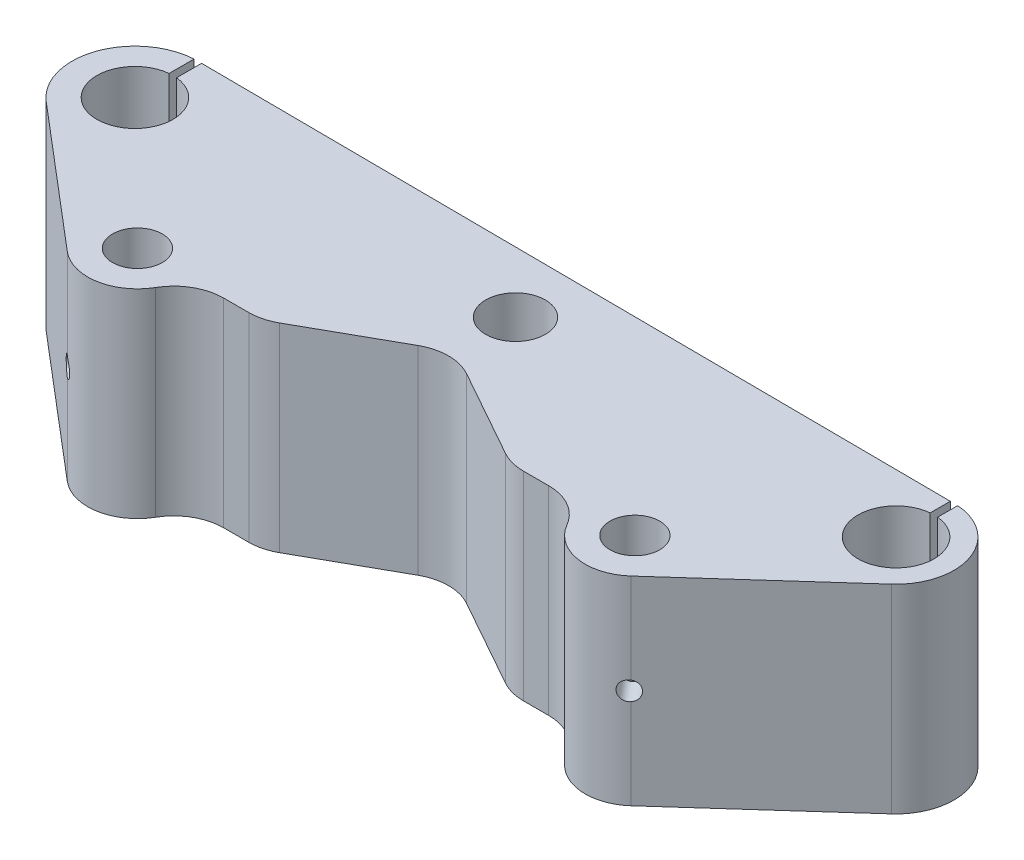
SolidWorks part; units mm, degrees
ref_plane "Płaszczyzna przednia" through (0, 0, 0) normal (0, 0, 1) x (1, 0, 0)
ref_plane "Płaszczyzna górna" through (0, 0, 0) normal (0, 1, 0) x (1, 0, 0)
ref_plane "Płaszczyzna prawa" through (0, 0, 0) normal (1, 0, 0) x (0, 0, -1)
sketch "Szkic1" plane through (0, 0, 0) normal (0, 1, 0) x (1, 0, 0)
  line L0 (-76.5, 12.65) -> (76.5761, 11.6498)
  line L1 (-84.6922, -9.639) -> (-56.476, -33.6198)
  line L2 (56.6792, -33.4423) -> (84.2813, -8.6703)
  line L3 (-50, -36) -> (50, -36)
  line L4 (-40, -26) -> (40, -26)
  circle A0 centre (-76.5, 0) radius 7.65
  circle A1 centre (76.5, 0) radius 7.65
  circle A2 centre (-76.5, 0) radius 12.65
  circle A3 centre (76.5, 0) radius 11.65
  circle A4 centre (0, 0) radius 6
  circle A5 centre (-50, -26) radius 5
  circle A6 centre (50, -26) radius 5
  circle A7 centre (-50, -26) radius 10
  circle A8 centre (50, -26) radius 10
  dimension "D1" = 15.3
  dimension "D2" = 15.3
  dimension "D7" = 12
  dimension "D8" = 10
  dimension "D9" = 100
  dimension "D3" = 153
  dimension "D4" = 76.5
  dimension "D10" = 50
  dimension "D11" = 26
  dimension "D5" = 5
  dimension "D6" = 4
  dimension "D12" = 5
extrude "Dodanie-wyciągnięcie1" add sketch "Szkic1" along normal blind 40 contours A2 A0 | A8 L2 A3 L0 A2 L1 A7 L3 A4 | A7 A5 | A8 A6 | A3 A1 region at (-76.4197, 0, -12.2917) region at (-0.0031, 0, 6.5837) region at (84.5309, 0, -7.9786) region at (-54.0789, 0, 17.1804) region at (53.475, 0, 35.0746)
sketch "Szkic2" plane through (0, 0, 0) normal (0, -1, 0) x (1, 0, 0)
  circle A0 centre (0, 0) radius 11
  dimension "D1" = 22
extrude "Wytnij-wyciągnięcie1" cut sketch "Szkic2" against normal blind 5
sketch "Szkic3" plane through (0, 5, 0) normal (0, -1, 0) x (1, 0, 0)
  line L0 (0, 0) -> (-5.6569, 5.6569) construction
  line L1 (0, 0) -> (0, 9.4855) construction
  circle A0 centre (0, 0) radius 8 construction
  circle A1 centre (-5.6569, 5.6569) radius 1.25
  circle A2 centre (5.6569, 5.6569) radius 1.25
  circle A3 centre (5.6569, -5.6569) radius 1.25
  circle A4 centre (-5.6569, -5.6569) radius 1.25
  point P15 (0, 0)
  dimension "D1" = 16
  dimension "D2" = 2.5
  dimension "D3" = 45
  dimension "D4" = 4
extrude "Wytnij-wyciągnięcie2" cut sketch "Szkic3" against normal blind 10
sketch "Szkic4" plane through (0, 40, 0) normal (0, 1, 0) x (1, 0, 0)
  line L0 (-25, -26) -> (0, -12)
  line L1 (-40, -26) -> (40, -26) construction
  line L2 (0, -12) -> (25, -26)
  line L3 (25, -26) -> (-25, -26)
  dimension "D1" = 14
  dimension "D2" = 50
extrude "Wytnij-wyciągnięcie3" cut sketch "Szkic4" against normal through all
fillet "Zaokrąglenie1" radius 10 5 edges at (40, 20, 26) (-40, 20, 26) (25, 20, 26) (0, 20, 12) (-25, 20, 26)
sketch "Szkic5" plane through (-40.2754, 0, 47.3886) normal (-0.6476, 0, 0.762) x (0.762, 0, 0.6476)
  line L0 (-16.2613, 40) -> (-26.2613, 40) construction
  line L1 (-16.2613, 40) -> (-26.2613, 40)
  line L2 (-21.2613, 40) -> (-21.2613, 0) construction
  circle A0 centre (-21.2613, 20) radius 1.9
  dimension "D1" = 3.8
extrude "Wytnij-wyciągnięcie4" cut sketch "Szkic5" against normal blind 20 contours A0
mirror "Lustro1" about plane through (0, 0, 0) normal (1, 0, 0) of "Wytnij-wyciągnięcie4"
sketch "Szkic6" plane through (0, 40, 0) normal (0, 1, 0) x (1, 0, 0)
  line L0 (0, 0) -> (0, 20.6321) construction
  line L1 (-75.75, 7.6131) -> (-75.75, 16.4542)
  line L2 (-75.75, 16.4542) -> (-77.25, 16.4542)
  line L3 (-77.25, 16.4542) -> (-77.25, 7.6131)
  line L4 (77.25, 16.4542) -> (77.25, 7.6131)
  line L5 (75.75, 16.4542) -> (77.25, 16.4542)
  line L6 (75.75, 7.6131) -> (75.75, 16.4542)
  circle A0 centre (76.5, 0) radius 7.65 construction
  circle A1 centre (-76.5, 0) radius 7.65 construction
  circle A2 centre (76.5, 0) radius 7.65
  circle A3 centre (-76.5, 0) radius 7.65
  arc M10 (84.2813, -8.6703) -> (76.5761, 11.6498) centre (76.5, 0) ccw
  line M11 (76.5761, 11.6498) -> (-76.5, 12.65)
  arc M12 (-76.5, 12.65) -> (-84.6922, -9.639) centre (-76.5, 0) ccw
  circle M20 centre (-76.5, 0) radius 7.65
  circle M23 centre (76.5, 0) radius 7.65
  dimension "D1" = 0.75
  dimension "D2" = 1.5
extrude "Wytnij-wyciągnięcie5" cut sketch "Szkic6" against normal through all contours L3 L1 M12 M20 M11 | L6 L4 M23 M10 M11 region at (-76.4997, 40, -10.1414) region at (76.4993, 40, -9.6425)
